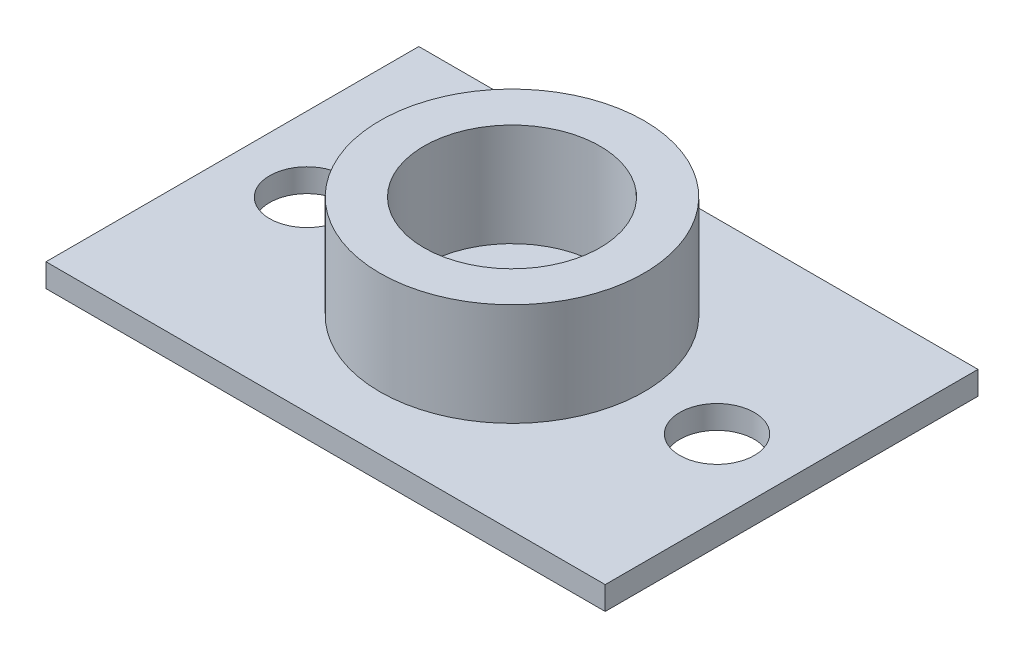
SolidWorks part; units mm, degrees
ref_plane "前视" through (0, 0, 0) normal (0, 0, 1) x (1, 0, 0)
ref_plane "上视" through (0, 0, 0) normal (0, 1, 0) x (1, 0, 0)
ref_plane "右视" through (0, 0, 0) normal (1, 0, 0) x (0, 0, -1)
sketch "Sketch1" plane through (0, 0, 0) normal (0, 1, 0) x (1, 0, 0)
  line L1 (-25.8417, 12.7) -> (12.2583, 12.7)
  line L2 (-25.8417, 12.7) -> (-25.8417, -12.7)
  line L3 (-25.8417, -12.7) -> (12.2583, -12.7)
  line L4 (12.2583, 12.7) -> (12.2583, -12.7)
  dimension "D1" = 25.4
  dimension "D2" = 38.1
extrude "Boss-Extrude1" add sketch "Sketch1" along normal blind 1.5875
ref_point "Point1"
sketch "Sketch3" plane through (0, 1.5875, 0) normal (0, 1, 0) x (1, 0, 0)
  circle A0 centre (-6.7917, 0) radius 9
  circle A1 centre (-6.7917, 0) radius 6
  dimension "D1" = 3
  dimension "D2" = 12
extrude "Boss-Extrude2" add sketch "Sketch3" along normal blind 7
ref_axis "Axis1" through (12.2583, 1.5875, 0) along (-1, 0, 0)
sketch "Sketch4" plane through (0, 1.5875, 0) normal (0, 1, 0) x (1, 0, 0)
  line L0 (12.2583, -12.7) -> (12.2583, 12.7) construction
  line L1 (-25.8417, 12.7) -> (-25.8417, -12.7) construction
  circle A0 centre (7.1783, 0) radius 2.54
  circle A1 centre (-20.7617, 0) radius 2.54
  point P0 (7.1783, 0)
  point P1 (12.2583, 0)
  point P4 (-20.7617, 0)
  dimension "D1" = 5.08
  dimension "D2" = 5.08
extrude "Cut-Extrude1" cut sketch "Sketch4" against normal through all
